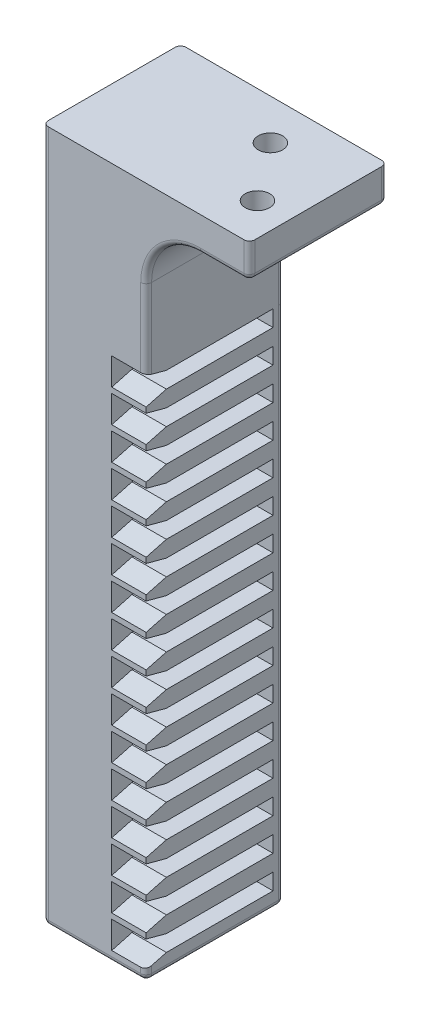
SolidWorks part; units mm, degrees
ref_plane "Front Plane" through (0, 0, 0) normal (0, 0, 1) x (1, 0, 0)
ref_plane "Top Plane" through (0, 0, 0) normal (0, 1, 0) x (1, 0, 0)
ref_plane "Right Plane" through (0, 0, 0) normal (1, 0, 0) x (0, 0, -1)
sketch "Sketch1" plane through (0, 0, 0) normal (0, 0, 1) x (1, 0, 0)
  line L0 (0, 0) -> (38.1, 0)
  line L1 (38.1, 0) -> (38.1, -6.35)
  line L2 (38.1, -6.35) -> (19.05, -6.35)
  line L3 (19.05, -6.35) -> (19.05, -31.75)
  line L4 (19.05, -31.75) -> (12.7, -31.75)
  line L5 (12.7, -31.75) -> (12.7, -34.75)
  line L6 (12.7, -34.75) -> (19.05, -34.75)
  line L7 (19.05, -34.75) -> (19.05, -37.75)
  line L8 (19.05, -37.75) -> (12.7, -37.75)
  line L9 (12.7, -37.75) -> (12.7, -40.75)
  line L10 (12.7, -40.75) -> (19.05, -40.75)
  line L11 (19.05, -40.75) -> (19.05, -43.75)
  line L12 (19.05, -31.75) -> (19.05, -37.75) construction
  line L13 (19.05, -43.75) -> (12.7, -43.75)
  line L14 (12.7, -43.75) -> (12.7, -46.75)
  line L15 (12.7, -46.75) -> (19.05, -46.75)
  line L16 (19.05, -46.75) -> (19.05, -49.75)
  line L17 (19.05, -49.75) -> (12.7, -49.75)
  line L18 (12.7, -49.75) -> (12.7, -52.75)
  line L19 (12.7, -52.75) -> (19.05, -52.75)
  line L20 (19.05, -52.75) -> (19.05, -55.75)
  line L21 (19.05, -55.75) -> (12.7, -55.75)
  line L22 (12.7, -55.75) -> (12.7, -58.75)
  line L23 (12.7, -58.75) -> (19.05, -58.75)
  line L24 (19.05, -58.75) -> (19.05, -61.75)
  line L25 (19.05, -61.75) -> (12.7, -61.75)
  line L26 (12.7, -61.75) -> (12.7, -64.75)
  line L27 (12.7, -64.75) -> (19.05, -64.75)
  line L28 (19.05, -64.75) -> (19.05, -67.75)
  line L29 (19.05, -67.75) -> (12.7, -67.75)
  line L30 (12.7, -67.75) -> (12.7, -70.75)
  line L31 (12.7, -70.75) -> (19.05, -70.75)
  line L32 (19.05, -70.75) -> (19.05, -73.75)
  line L33 (19.05, -73.75) -> (12.7, -73.75)
  line L34 (12.7, -73.75) -> (12.7, -76.75)
  line L35 (12.7, -76.75) -> (19.05, -76.75)
  line L36 (19.05, -76.75) -> (19.05, -79.75)
  line L37 (19.05, -79.75) -> (12.7, -79.75)
  line L38 (12.7, -79.75) -> (12.7, -82.75)
  line L39 (12.7, -82.75) -> (19.05, -82.75)
  line L40 (19.05, -82.75) -> (19.05, -85.75)
  line L41 (19.05, -85.75) -> (12.7, -85.75)
  line L42 (12.7, -85.75) -> (12.7, -88.75)
  line L43 (12.7, -88.75) -> (19.05, -88.75)
  line L44 (19.05, -88.75) -> (19.05, -91.75)
  line L45 (19.05, -91.75) -> (12.7, -91.75)
  line L46 (12.7, -91.75) -> (12.7, -94.75)
  line L47 (12.7, -94.75) -> (19.05, -94.75)
  line L48 (19.05, -94.75) -> (19.05, -97.75)
  line L49 (19.05, -97.75) -> (12.7, -97.75)
  line L50 (12.7, -97.75) -> (12.7, -100.75)
  line L51 (12.7, -100.75) -> (19.05, -100.75)
  line L52 (19.05, -100.75) -> (19.05, -103.75)
  line L53 (19.05, -103.75) -> (12.7, -103.75)
  line L54 (12.7, -103.75) -> (12.7, -106.75)
  line L55 (12.7, -106.75) -> (19.05, -106.75)
  line L56 (19.05, -106.75) -> (19.05, -109.75)
  line L57 (19.05, -109.75) -> (12.7, -109.75)
  line L58 (12.7, -109.75) -> (12.7, -112.75)
  line L59 (12.7, -112.75) -> (19.05, -112.75)
  line L60 (19.05, -112.75) -> (19.05, -115.75)
  line L61 (19.05, -115.75) -> (12.7, -115.75)
  line L62 (12.7, -115.75) -> (12.7, -118.75)
  line L63 (12.7, -118.75) -> (19.05, -118.75)
  line L64 (19.05, -118.75) -> (19.05, -121.75)
  line L65 (19.05, -121.75) -> (12.7, -121.75)
  line L66 (12.7, -121.75) -> (12.7, -124.75)
  line L67 (12.7, -124.75) -> (19.05, -124.75)
  line L68 (19.05, -124.75) -> (19.05, -127.75)
  line L69 (19.05, -127.75) -> (0, -127.75)
  line L70 (0, 0) -> (0, -127.75)
  dimension "D1" = 25.4
  dimension "D2" = 6.35
  dimension "D3" = 38.1
  dimension "D4" = 19.05
  dimension "D5" = 3
  dimension "D6" = 12.7
  dimension "D7" = 16
extrude "Boss-Extrude1" add sketch "Sketch1" along normal mid plane 25.4 contours L3 L4 L5 L6 L7 L8 L9 L10 L11 L13 L14 L15 L16 L17 L18 L19 L20 L21 L22 L23 L24 L25 L26 L27 L28 L29 L30 L31 L32 L33 L34 L35 L36 L37 L38 L39 L40 L41 L42 L43 L44 L45 L46 L47 L48 L49 L50 L51 L52 L53 L54 L55 L56 L57 L58 L59 L60 L61 L62 L63 L64 L65 L66 L67 L68 L69 L70 L0 L1 L2
chamfer "Chamfer1" distance 1 angle 75 32 edges at (15.875, -124.75, 12.7) (15.875, -121.75, 12.7) (15.875, -118.75, 12.7) (15.875, -115.75, 12.7) (15.875, -112.75, 12.7) (15.875, -109.75, 12.7) (15.875, -106.75, 12.7) (15.875, -103.75, 12.7) (15.875, -100.75, 12.7) (15.875, -97.75, 12.7) (15.875, -94.75, 12.7) (15.875, -91.75, 12.7) (15.875, -88.75, 12.7) (15.875, -85.75, 12.7) (15.875, -82.75, 12.7) (15.875, -79.75, 12.7) (15.875, -76.75, 12.7) (15.875, -73.75, 12.7) (15.875, -70.75, 12.7) (15.875, -67.75, 12.7) (15.875, -64.75, 12.7) (15.875, -61.75, 12.7) (15.875, -58.75, 12.7) (15.875, -55.75, 12.7) (15.875, -52.75, 12.7) (15.875, -46.75, 12.7) (15.875, -49.75, 12.7) (15.875, -43.75, 12.7) (15.875, -40.75, 12.7) (15.875, -37.75, 12.7) (15.875, -34.75, 12.7) (15.875, -31.75, 12.7) first distance on face at (16.1471, -75.3743, 12.7)
fillet "Fillet1" radius 10 1 edges at (19.05, -6.35, 0)
fillet "Fillet2" radius 1 14 edges at (9.525, -127.75, -12.7) (0, -63.875, -12.7) (0, -63.875, 12.7) (0, -127.75, 0) (9.525, -127.75, 12.7) (33.575, -6.35, -12.7) (21.9789, -9.2789, -12.7) (33.575, -6.35, 12.7) (21.9789, -9.2789, 12.7) (38.1, -6.35, 0) (19.05, -24.05, -12.7) (19.05, -23.55, 12.7) (38.1, -3.175, -12.7) (38.1, -3.175, 12.7)
ref_plane "Plane1" through (0, -16.35, 0) normal (0, 1, 0) x (1, 0, 0)
sketch "Sketch2" plane through (0, -16.35, 0) normal (0, 1, 0) x (1, 0, 0)
  line L1 (37.1, -11.7) -> (19.05, 11.7) construction
  line L3 (19.05, 11.7) -> (24.05, 5.218)
  line L4 (24.05, 5.218) -> (32.1, -5.218)
  line L5 (32.1, -5.218) -> (37.1, -11.7)
  line L6 (37.1, 11.7) -> (37.1, -11.7) construction
  dimension "D1" = 5
sketch "Sketch3" plane through (0, -16.35, 0) normal (0, 1, 0) x (1, 0, 0)
  point P0 (24.05, 5.218)
  point P1 (32.1, -5.218)
hole_wizard "CSK for M4 Flat Head Machine Screw1" positions "Sketch3" profile "Sketch4" countersink size "M4" standard "ANSI Metric" end condition through all
sketch "Sketch4" plane through (24.05, -16.35, -5.218) normal (1, 0, 0) x (0, 0, -1)
  line L0 (0, 0) -> (0, 16.35)
  line L1 (0, 16.35) -> (2.25, 16.35)
  line L2 (2.25, 16.35) -> (2.25, 2.45)
  line L3 (2.25, 2.45) -> (4.7, 0)
  line L5 (4.7, 0) -> (0, 0)
  line L6 (-2.25, 2.45) -> (-4.7, 0) construction
  line L11 (0, -6.35) -> (0, 107.95) construction
  dimension "Thru Hole Dia." = 4.5
  dimension "Thru Hole Depth" = 16.35
  dimension "Near C'Sink Dia." = 9.4
  dimension "Near C'Sink Angle" = 90
sketch "Sketch5" plane through (0, -31.75, 0) normal (0, -1, 0) x (1, 0, 0)
  line L0 (19.05, 8.9679) -> (19.05, -11.7) construction
  line L1 (12.7, -12.7) -> (19.05, -12.7)
  line L2 (12.7, -12.7) -> (12.7, -10.7)
  line L3 (12.7, -10.7) -> (19.05, -10.7)
  line L4 (19.05, -12.7) -> (19.05, -10.7)
  dimension "D1" = 2
extrude "Boss-Extrude2" add sketch "Sketch5" along normal up to surface (93 mm away) up to face at (15.875, -124.75, -1.866)
fillet "Fillet3" radius 1 5 edges at (19.05, -126.25, 12.7) (19.05, -127.4571, 12.4071) (19.05, -127.75, 0) (19.05, -127.4571, -12.4071) (19.05, -79.25, -12.7)
